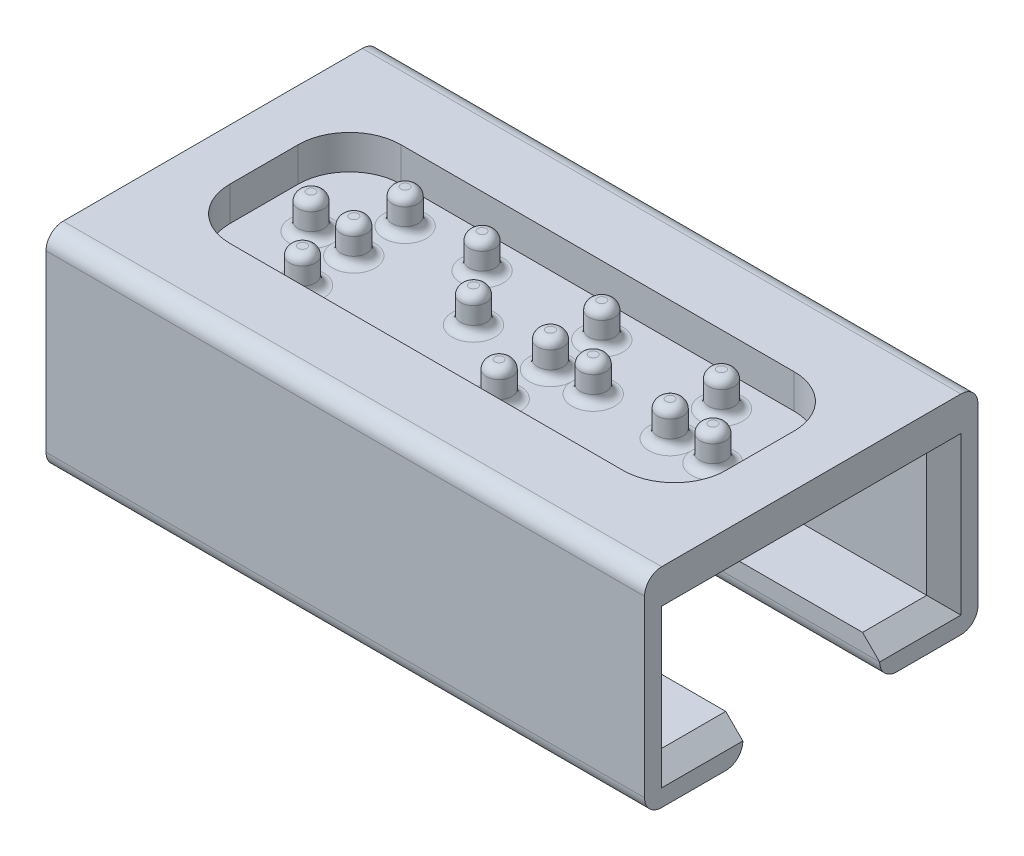
SolidWorks part; units mm, degrees
ref_plane "Front Plane" through (0, 0, 0) normal (0, 0, 1) x (1, 0, 0)
ref_plane "Top Plane" through (0, 0, 0) normal (0, 1, 0) x (1, 0, 0)
ref_plane "Right Plane" through (0, 0, 0) normal (1, 0, 0) x (0, 0, -1)
sketch "Sketch1" plane through (0, 0, 0) normal (0, 1, 0) x (1, 0, 0)
  line L0 (2.5, 3.75) -> (2.5, 6)
  line L1 (0, 0) -> (1.75, 0)
  line L2 (0, 0.75) -> (0, 2.25)
  line L3 (0.75, 6) -> (1.75, 6)
  line L4 (2.5, 0.75) -> (2.5, 2.25)
  line L5 (0, 3.75) -> (0, 5.25)
  line L6 (11.75, 8) -> (11.75, -2) construction
  line L7 (0.25, -2) -> (23.25, -2)
  line L8 (-2.75, 1) -> (-2.75, 5)
  line L9 (0.25, 8) -> (23.25, 8)
  line L10 (26.25, 1) -> (26.25, 5)
  line L11 (9.5, 3) -> (14, 3) construction
  line L12 (-5.75, 3) -> (29.25, 3) construction
  line L13 (-5.75, 12.75) -> (29.25, 12.75)
  line L14 (-5.75, 12.75) -> (-5.75, -6.75)
  line L15 (-5.75, -6.75) -> (29.25, -6.75)
  line L16 (29.25, 12.75) -> (29.25, -6.75)
  line L17 (-2.2121, 12.75) -> (-2.2121, 10.75) construction
  line L18 (-5.75, 12.75) -> (29.25, 12.75)
  line L19 (-5.75, 12.75) -> (-5.75, 10.75)
  line L20 (-5.75, 10.75) -> (29.25, 10.75)
  line L21 (29.25, 12.75) -> (29.25, 10.75)
  circle A0 centre (0, 6) radius 0.75
  circle A1 centre (2.5, 6) radius 0.75
  circle A2 centre (2.5, 3) radius 0.75
  circle A3 centre (2.5, 0) radius 0.75
  circle A4 centre (0, 3) radius 0.75
  circle A5 centre (0, 0) radius 0.75
  circle A6 centre (7, 6) radius 0.75
  circle A7 centre (9.5, 6) radius 0.75
  circle A8 centre (7, 3) radius 0.75
  circle A9 centre (9.5, 3) radius 0.75
  circle A10 centre (7, 0) radius 0.75
  circle A11 centre (9.5, 0) radius 0.75
  circle A12 centre (14, 6) radius 0.75
  circle A13 centre (16.5, 6) radius 0.75
  circle A14 centre (14, 3) radius 0.75
  circle A15 centre (16.5, 3) radius 0.75
  circle A16 centre (14, 0) radius 0.75
  circle A17 centre (16.5, 0) radius 0.75
  circle A18 centre (21, 6) radius 0.75
  circle A19 centre (23.5, 6) radius 0.75
  circle A20 centre (21, 3) radius 0.75
  circle A21 centre (23.5, 3) radius 0.75
  circle A22 centre (21, 0) radius 0.75
  circle A23 centre (23.5, 0) radius 0.75
  arc A24 (23.25, -2) -> (26.25, 1) centre (23.25, 1) ccw
  arc A25 (26.25, 5) -> (23.25, 8) centre (23.25, 5) ccw
  arc A26 (0.25, -2) -> (-2.75, 1) centre (0.25, 1) cw
  arc A27 (-2.75, 5) -> (0.25, 8) centre (0.25, 5) cw
  point P69 (26.25, 8)
  point P72 (-2.75, -2)
  point P75 (-2.75, 8)
  point P78 (11.75, 3)
  dimension "D3" = 1.5
  dimension "D9" = 3
  dimension "D1" = 6
  dimension "D2" = 2.5
  dimension "D7" = 10
  dimension "D8" = 29
  dimension "D10" = 19.5
  dimension "D11" = 35
  dimension "D12" = 2
  dimension "D4" = 2
  dimension "D5" = 3
  dimension "D6" = 4
extrude "Boss-Extrude1" add sketch "Sketch1" along normal blind 2 contours A4 | A1 | A2 | A3 | A6 | A9 | A12 | A14 | A16 | A15 | A18 | A20 | A21 region at (2.5, 0, -3) region at (1.9847, 0, -5.4847) region at (2.5, 0, 0) region at (0, 0, -3) region at (7, 0, -6) region at (9.5, 0, -3) region at (14, 0, -6) region at (14, 0, -3) region at (16.5, 0, -3) region at (14, 0, 0) region at (21, 0, -6) region at (21, 0, -3) region at (23.5, 0, -3)
extrude "Boss-Extrude2" add sketch "Sketch1<3>" against normal blind 1 contours A27 L8 A26 L7 A24 L10 A25 L9 A23 A22 A21 A20 A19 A18 A17 A16 A15 A14 A13 A12 A11 A10 A9 A8 A7 A6 A5 L2 A4 L5 A0 L3 | L20 L14 L15 L16 L8 A27 L9 A25 L10 A24 L7 A26 | A5 L1 A3 L4 A2 L0 A1 L3 A0 L5 A4 L2 | A0 | A4 | A5 | A10 | A8 | A17 | A13 | A22 | A23 | A19 | A9 | A6 | A7 | A12 | A14 | A15 | A16 | A20 | A18 | A21 | A1 | A11 | A2 | A3 | L14 L20 L16 L13 region at (1.25, 0, -3) region at (2.5, 0, -3) region at (1.9847, 0, -5.4847) region at (2.5, 0, 0) region at (0, 0, -6) region at (-0.5153, 0, 0.5153) region at (0, 0, -3) region at (12.2771, 0, -3) region at (11.75, 0, -11.75) region at (11.75, 0, -10.3587) region at (7, 0, -6) region at (9.5, 0, -6) region at (7, 0, -3) region at (9.5, 0, -3) region at (7, 0, 0) region at (9.5, 0, 0) region at (14, 0, -6) region at (16.5, 0, -6) region at (14, 0, -3) region at (16.5, 0, -3) region at (14, 0, 0) region at (16.5, 0, 0) region at (21, 0, -6) region at (23.5, 0, -6) region at (21, 0, -3) region at (23.5, 0, -3) region at (21, 0, 0) region at (23.5, 0, 0)
sketch "Sketch1<3>" plane through (0, 0, 0) normal (0, 1, 0) x (1, 0, 0) same geometry as "Sketch1"
fillet "Fillet1" radius 0.5 26 edges at (0, 0, -2.25) (0, 2, -2.25) (2.5, 0, -5.25) (2.5, 2, -5.25) (2.5, 0, -2.25) (2.5, 2, -2.25) (2.5, 0, 0.75) (2.5, 2, 0.75) (7, 0, -5.25) (7, 2, -5.25) (9.5, 0, -2.25) (9.5, 2, -2.25) (14, 0, -5.25) (14, 2, -5.25) (14, 0, -2.25) (14, 2, -2.25) (14, 0, 0.75) (14, 2, 0.75) (16.5, 0, -2.25) (16.5, 2, -2.25) (21, 0, -5.25) (21, 2, -5.25) (21, 0, -2.25) (21, 2, -2.25) (23.5, 0, -2.25) (23.5, 2, -2.25)
extrude "Boss-Extrude3" add sketch "Sketch1<4>" along normal blind 2 contours L20 L14 L15 L16 L8 A27 L9 A25 L10 A24 L7 A26 | L14 L20 L16 L13 region at (11.75, 0, -11.75) region at (11.75, 0, -10.3587)
sketch "Sketch1<4>" plane through (0, 0, 0) normal (0, 1, 0) x (1, 0, 0) same geometry as "Sketch1"
extrude "Boss-Extrude4" add sketch "Sketch1<5>" against normal blind 8.2 contours L14 L20 L16 L13 region at (11.75, 0, -11.75)
sketch "Sketch1<5>" plane through (0, 0, 0) normal (0, 1, 0) x (1, 0, 0) same geometry as "Sketch1"
ref_plane "Plane1" through (0, 0, -3) normal (0, 0, -1) x (-1, 0, 0)
mirror "Mirror1" about plane through (0, 0, -3) normal (0, 0, -1) of "Boss-Extrude4"
sketch "Sketch2" plane through (0, -8.2, 0) normal (0, -1, 0) x (1, 0, 0)
  line L0 (29.25, -3) -> (14.25, -3) construction
  line L1 (29.25, -12.75) -> (-5.75, -12.75)
  line L2 (29.25, -12.75) -> (29.25, 6.75)
  line L3 (29.25, 6.75) -> (-5.75, 6.75)
  line L4 (-5.75, -12.75) -> (-5.75, 6.75)
  line L5 (-5.61, -3) -> (5.61, -3) construction
  line L6 (11.75, 1) -> (11.75, -3) construction
  line L7 (29.25, -3) -> (-5.75, -3)
  line L8 (29.25, -3) -> (29.25, 1)
  line L9 (29.25, 1) -> (-5.75, 1)
  line L10 (-5.75, -3) -> (-5.75, 1)
  line L11 (14.25, -3) -> (14.25, 4.75) construction
  line L12 (-5.75, 4.75) -> (29.25, 4.75) construction
  line L13 (14.25, 4.75) -> (10.5, 1)
  line L14 (10.5, 1) -> (1.385, 1)
  line L15 (1.385, 1) -> (-5.75, 4.75)
  line L16 (-5.75, 4.75) -> (14.25, 4.75)
  line M3 (-5.75, -10.75) -> (-5.75, -12.75)
  line M4 (-5.75, -12.75) -> (29.25, -12.75)
  line M5 (29.25, -12.75) -> (29.25, -10.75)
  line M6 (29.25, -10.75) -> (-5.75, -10.75)
  dimension "D1" = 15
  dimension "D2" = 4
extrude "Boss-Extrude5" add sketch "Sketch2" against normal up to next contours L16 L15 L9 L13 region at (4.9908, -8.2, 3.1087)
mirror "Mirror2" about plane through (0, 0, -3) normal (0, 0, -1) of "Boss-Extrude5"
extrude "Boss-Extrude6" add sketch "Sketch2<3>" along normal blind 2 contours M6 M3 M4 M5 | L2 L7 L4 M6 | L2 L9 L4 L7 | L16 L15 L9 L13 | L4 L16 L13 L9 L2 L3 | L9 L15 L4 region at (11.75, -8.2, -11.75) region at (11.75, -8.2, -6.875) region at (11.75, -8.2, -1) region at (16.0363, -8.2, 4.352) region at (-3.3717, -8.2, 2.25) region at (4.9908, -8.2, 3.1087)
sketch "Sketch2<3>" plane through (0, -8.2, 0) normal (0, -1, 0) x (1, 0, 0) same geometry as "Sketch2"
fillet "Fillet2" radius 1 4 edges at (11.75, -10.2, 6.75) (11.75, -10.2, -12.75) (11.75, 2, -12.75) (11.75, 2, 6.75)
chamfer "Chamfer1" distance 1 angle 45 2 edges at (-5.75, -1, -3) (-5.75, -8.2, -3)
extrude "Cut-Extrude1" cut sketch "Sketch2<4>" along normal blind 2 contours L2 L9 L4 L7 region at (11.75, -8.2, -1)
sketch "Sketch2<4>" plane through (0, -8.2, 0) normal (0, -1, 0) x (1, 0, 0) same geometry as "Sketch2"
mirror "Mirror3" about plane through (0, 0, -3) normal (0, 0, -1) of "Cut-Extrude1"
fillet "Fillet3" radius 1 2 edges at (11.75, -10.2, -7) (11.75, -10.2, 1)
chamfer "Chamfer2" distance 1 angle 45 5 edges at (29.25, -8.2, 2.875) (29.25, -4.6, 4.75) (29.25, -8.2, -8.875) (29.25, -4.6, -10.75) (29.25, -1, -3)
